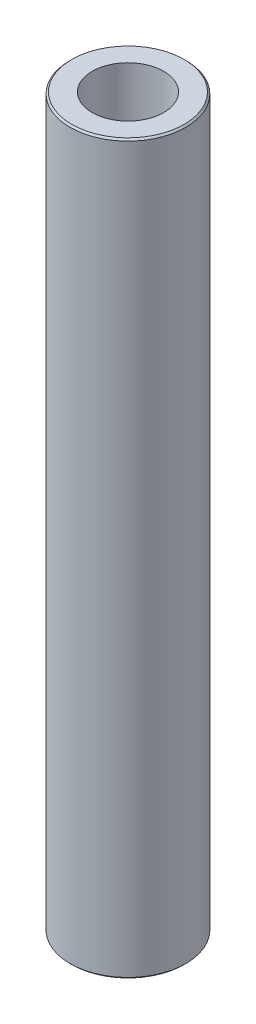
SolidWorks part; units mm, degrees
ref_plane "Front Plane" through (0, 0, 0) normal (0, 0, 1) x (1, 0, 0)
ref_plane "Top Plane" through (0, 0, 0) normal (0, 1, 0) x (1, 0, 0)
ref_plane "Right Plane" through (0, 0, 0) normal (1, 0, 0) x (0, 0, -1)
sketch "Sketch1" plane through (0, 0, 0) normal (0, 1, 0) x (1, 0, 0)
  circle A0 centre (0, 0) radius 7.5
  dimension "SHAFT_OD" = 15
extrude "Boss-Extrude1" add sketch "Sketch1" along normal blind 94.204
sketch "Sketch2" plane through (0, 0, 0) normal (0, 1, 0) x (1, 0, 0)
  circle A0 centre (0, 0) radius 4.6318
  dimension "BORE_D" = 9.2637
extrude "Cut-Extrude1" cut sketch "Sketch2" along normal through all
chamfer "Chamfer1" distance 0.2173 angle 45 2 edges at (0, 94.204, 7.5) (0, 0, 7.5)
